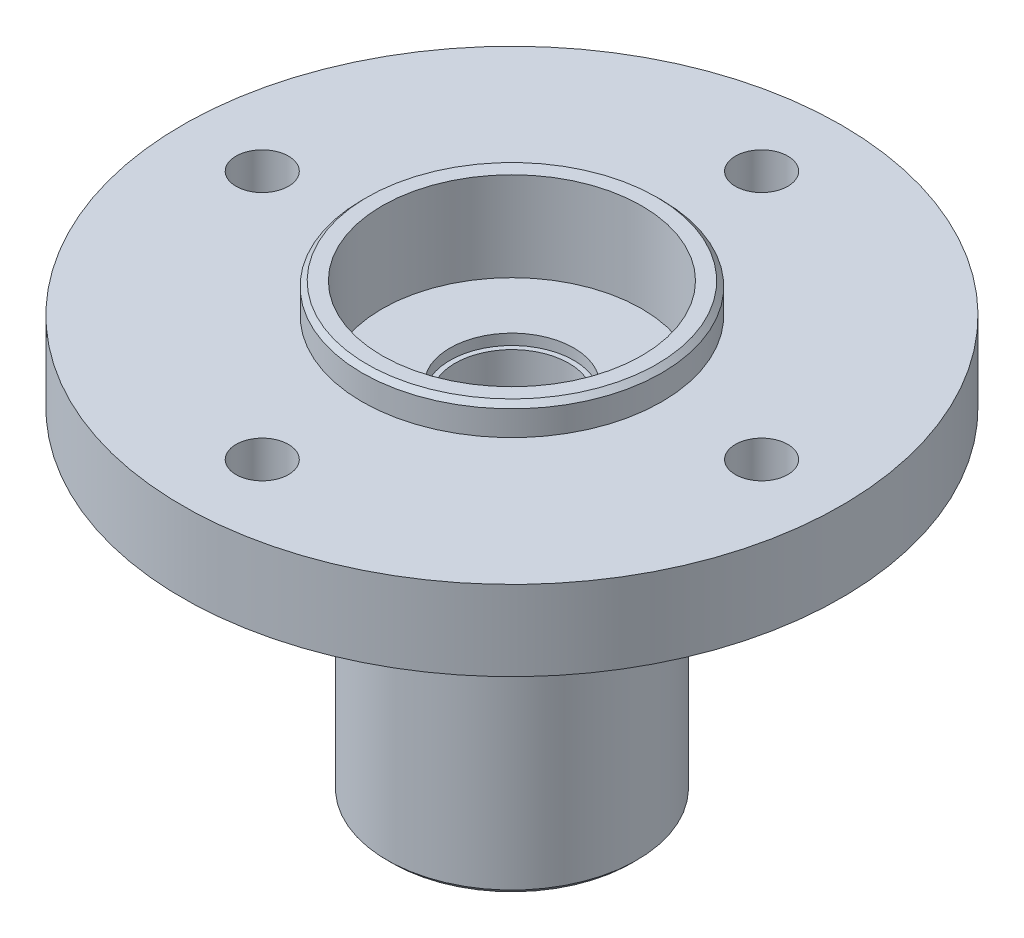
SolidWorks part; units mm, degrees
material "7050-T7451"
ref_plane "Płaszczyzna przednia" through (0, 0, 0) normal (0, 0, 1) x (1, 0, 0)
ref_plane "Płaszczyzna górna" through (0, 0, 0) normal (0, 1, 0) x (1, 0, 0)
ref_plane "Płaszczyzna prawa" through (0, 0, 0) normal (1, 0, 0) x (0, 0, -1)
sketch "Szkic1" plane through (0, 0, 0) normal (0, 0, 1) x (1, 0, 0)
  line L0 (0, 0) -> (0, 84.3909) construction
  line L1 (30, 80.9231) -> (66, 80.9231)
  line L2 (66, 80.9231) -> (66, 64.9231)
  line L3 (66, 64.9231) -> (25, 64.9231)
  line L4 (25, 64.9231) -> (25, 39.9231)
  line L8 (25, 39.9231) -> (25, -1.0769)
  line L9 (24, -2.0769) -> (8.9, -2.0769)
  line L10 (8.9, -2.0769) -> (8.9, -0.0769)
  line L11 (8.9, -0.0769) -> (11.4, -0.0769)
  line L12 (11.4, -0.0769) -> (11.4, 66.9231)
  line L13 (11.4, 66.9231) -> (12.4, 66.9231)
  line L14 (12.4, 66.9231) -> (12.4, 69.0731)
  line L15 (12.4, 69.0731) -> (26, 69.0731)
  line L16 (26, 69.0731) -> (26, 80.9231)
  line L17 (26, 80.9231) -> (26, 86.9231)
  line L18 (26, 86.9231) -> (29, 86.9231)
  line L19 (30, 85.9231) -> (30, 80.9231)
  line L20 (29, 86.9231) -> (30, 85.9231)
  line L21 (25, -1.0769) -> (24, -2.0769)
  point P5 (25, -2.0769)
  point P19 (30, 86.9231)
  dimension "D2" = 26
  dimension "D3" = 16
  dimension "D4" = 25
  dimension "D5" = 25
  dimension "D6" = 40
  dimension "D7" = 11.4
  dimension "D8" = 4.15
  dimension "D9" = 67
  dimension "D11" = 2
  dimension "D12" = 2.5
  dimension "D14" = 1
  dimension "D15" = 2.15
  dimension "D16" = 4
  dimension "D17" = 6
revolve "Obrót1" add sketch "Szkic1" angle 360 about L0
sketch "Szkic2" plane through (0, 80.9231, 0) normal (0, 1, 0) x (1, 0, 0)
  point P0 (-50, 0)
  point P5 (0, 50)
  point P6 (50, 0)
  point P7 (0, -50)
  dimension "D1" = 50
  dimension "D2" = 4
hole_wizard "Otwór gwintowany M12x1.51" positions "Szkic 3D2" profile "Szkic4" tap size "M12x1.5" standard "DIN" end condition up to next
sketch3d "Szkic 3D2"
  point P0 (-50, 80.9231, 0)
  point P3 (0, 80.9231, -50)
  point P6 (50, 80.9231, 0)
  point P9 (0, 80.9231, 50)
sketch "Szkic4" plane through (-50, 80.9231, 0) normal (1, 0, 0) x (0, 0, 1)
  line L0 (0, 0) -> (0, 16)
  line L1 (0, 16) -> (5.25, 16)
  line L2 (5.25, 16) -> (5.25, 0)
  line L5 (5.25, 0) -> (0, 0)
  line L11 (0, -6.35) -> (0, 107.95) construction
  dimension "Średnica otworu gwintowanego na wylot" = 10.5
  dimension "Głębokość otworu gwintowanego na wylot" = 16
cosmetic thread "Gwint otworu1" parameters "D2"=12
cosmetic thread "Gwint otworu2" parameters "D2"=12
cosmetic thread "Gwint otworu3" parameters "D2"=12
cosmetic thread "Gwint otworu4" parameters "D2"=12
